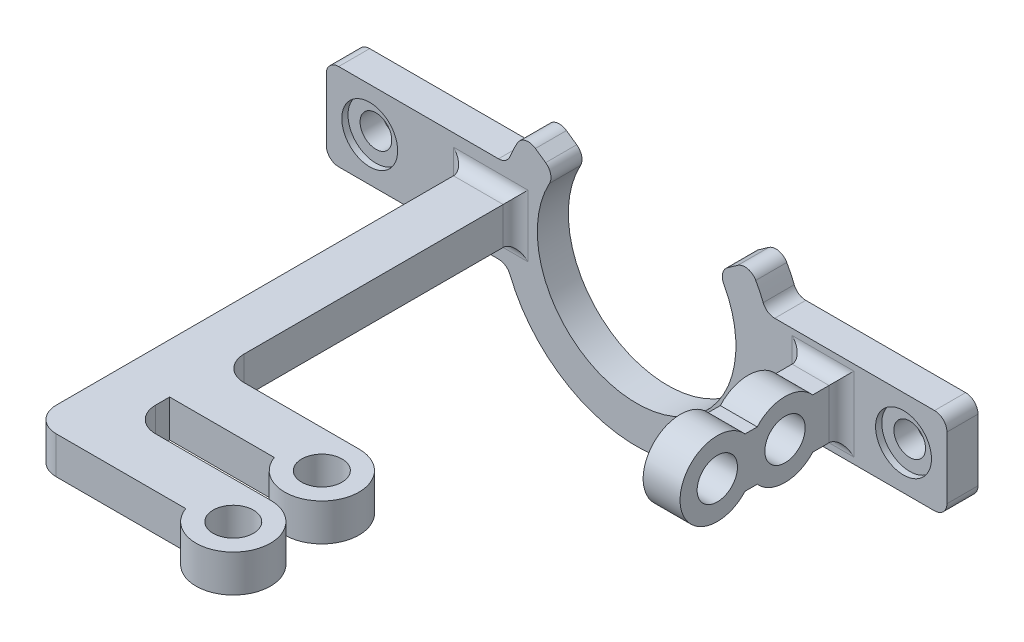
SolidWorks part; units mm, degrees
note: '?' marks a value the reader was unsure of.
ref_plane "Front Plane" through (0, 0, 0) normal (0, 0, 1) x (1, 0, 0)
ref_plane "Top Plane" through (0, 0, 0) normal (0, 1, 0) x (1, 0, 0)
ref_plane "Right Plane" through (0, 0, 0) normal (1, 0, 0) x (0, 0, -1)
sketch "Sketch1" plane through (0, 0, 0) normal (0, 0, 1) x (1, 0, 0)
  line L0 (100, 25) -> (100, 20)
  line L1 (100, 5) -> (100, 45) construction
  line L3 (98, 18) -> (72.2486, 18)
  line L4 (100, 25) -> (100, 30)
  line L5 (78.9438, 32) -> (98, 32)
  line L7 (78.9438, 32) -> (72.2486, 32)
  line L8 (54, 25) -> (106.793, 25) construction
  line L9 (50, 29) -> (50, 55.0668) construction
  line L16 (50, 25) -> (93.1322, 55.2015) construction
  line L17 (64.6534, 35.2604) -> (66.3009, 36.414)
  line L18 (50, 25) -> (6.8678, 55.2015) construction
  line L19 (46, 25) -> (-6.793, 25) construction
  line L20 (35.3466, 35.2604) -> (33.6991, 36.414)
  line L21 (21.0562, 32) -> (27.7514, 32)
  line L22 (2, 18) -> (27.7514, 18)
  line L23 (21.0562, 32) -> (2, 32)
  line L24 (0, 25) -> (0, 30)
  line L25 (0, 25) -> (0, 20)
  arc A0 (70.3945, 33.25) -> (69.1929, 35.7533) centre (50, 25) ccw
  arc A1 (35.955, 32.6641) -> (64.045, 32.6641) centre (50, 25) ccw
  arc A2 (29.6055, 16.75) -> (70.3945, 16.75) centre (50, 25) ccw
  circle A3 centre (93, 25) radius 2.55
  arc A14 (98, 32) -> (100, 30) centre (98, 30) cw
  arc A15 (98, 18) -> (100, 20) centre (98, 20) ccw
  arc A16 (72.2486, 18) -> (70.3945, 16.75) centre (72.2486, 16) ccw
  arc A17 (70.3945, 33.25) -> (72.2486, 32) centre (72.2486, 34) ccw
  arc A18 (64.6534, 35.2604) -> (64.045, 32.6641) centre (65.8006, 33.6221) ccw
  arc A19 (66.3009, 36.414) -> (69.1929, 35.7533) centre (67.4481, 34.7757) cw
  arc A21 (33.6991, 36.414) -> (30.8071, 35.7533) centre (32.5519, 34.7757) ccw
  arc A22 (35.3466, 35.2604) -> (35.955, 32.6641) centre (34.1994, 33.6221) cw
  arc A23 (29.6055, 33.25) -> (27.7514, 32) centre (27.7514, 34) cw
  arc A24 (27.7514, 18) -> (29.6055, 16.75) centre (27.7514, 16) cw
  arc A25 (2, 18) -> (0, 20) centre (2, 20) cw
  arc A26 (2, 32) -> (0, 30) centre (2, 30) ccw
  circle A27 centre (7, 25) radius 2.55
  arc A29 (29.6055, 33.25) -> (30.8071, 35.7533) centre (50, 25) cw
  point P30 (50, 3)
  point P31 (63.1064, 34.1772)
  point P35 (68.0213, 37.6187)
  point P39 (100, 32)
  point P73 (0, 32)
  point P74 (31.9787, 37.6187)
  point P75 (36.8936, 34.1772)
  dimension "D2" = 22
  dimension "D4" = 16
  dimension "D9" = 2
  dimension "D8" = 2
  dimension "D11" = 5.1
  dimension "D1" = 14
  dimension "D3" = 7
  dimension "D10" = 35
extrude "Boss-Extrude1" add sketch "Sketch1" along normal blind 5
fillet "Fillet2" [suppressed] radius 1
sketch "Sketch4" plane through (0, 0, 5) normal (0, 0, 1) x (1, 0, 0)
  circle A0 centre (93, 25) radius 4.5
  circle A1 centre (7, 25) radius 4.5
  dimension "D1" = 9
  dimension "D2" = 9
extrude "Cut-Extrude2" cut sketch "Sketch4" against normal blind 1
ref_axis "Axis1" through (93, 25, 4) along (0, 0, -1)?
ref_axis "Axis2" through (50, 25, 5) along (0, 0, -1)?
ref_plane "Plane1" through (0, 25, 0) normal (0, -1, 0) x (-1, 0, 0)
sketch "Sketch6" plane through (0, 25, 0) normal (0, -1, 0) x (-1, 0, 0)
  line L0 (-72.2486, -5) -> (-98, -5) construction
  line L1 (-77.0523, -5) -> (-83, -5)
  line L4 (-83, -5) -> (-83, -25)
  line L5 (-77.0523, -5) -> (-77.0523, -25)
  line L6 (-83, -25) -> (-77.0523, -25)
  line L7 (-93, -4) -> (-93, 0) construction
  dimension "D1" = 10
  dimension "D2" = 0
extrude "Boss-Extrude2" add sketch "Sketch6" along normal blind 4 and the other way blind 4
ref_plane "Plane2" through (77.0523, 21, 5) normal (1, 0, 0) x (0, 0, -1)
sketch "Sketch11" plane through (0, 0, 0) normal (0, 0, -1) x (-1, 0, 0)
  circle A0 centre (-93, 25) radius 4.5
  circle A1 centre (-7, 25) radius 4.5
  dimension "D1" = 9
  dimension "D2" = 9
extrude "Cut-Extrude3" cut sketch "Sketch11" against normal blind 0.5
thread "Thread1" [suppressed] pitch 0.8 start angle 0, offset 0, length 0, pitch 0.8, diameter 5.1
ref_plane "Plane3" through (90.45, 25, 4) normal (0, -1, 0) x (-1, 0, 0)
sketch "Thread Profile1" plane through (90.45, 25, 4) normal (0, -1, 0) x (-1, 0, 0)
  line L0 (0, 0) -> (0, 0.8) construction
  line L11 (0, 0) -> (0, 0.7)
  line L12 (0, 0.7) -> (-0.433, 0.45)
  line L13 (-0.433, 0.45) -> (-0.433, 0.25)
  line L15 (-0.433, 0.25) -> (0, 0)
  line L17 (-0.433, 0.35) -> (0, 0.35) construction
  point P2 (0, 0)
  dimension "Pitch" = 0.8
  dimension "Profile_Angle" = 60
  dimension "Profile_Land" = 0.2
  dimension "Profile_Height" = 0.433
sketch "Sketch16" plane through (0, 25, 0) normal (0, -1, 0) x (-1, 0, 0)
  line L0 (-27.7514, -5) -> (-2, -5) construction
  line L1 (-30.4943, -5) -> (-22.4943, -5)
  line L2 (-30.4943, -5) -> (-30.4943, -48.7321)
  line L3 (-30.4943, -75) -> (-26.4943, -75)
  line L4 (-22.4943, -5) -> (-22.4943, -71)
  line L5 (-30.4943, -60.7321) -> (-47.3614, -60.7321)
  line L6 (-30.4943, -75) -> (-47.3614, -75)
  line L8 (-34.4943, -67) -> (-53.0183, -67)
  line L10 (-53.0183, -52.7321) -> (-34.4943, -52.7321)
  line L11 (-30.4943, -60.7321) -> (-30.4943, -63)
  arc A0 (-53.0183, -67) -> (-47.3614, -75) centre (-53.0183, -73) ccw
  circle A1 centre (-53.0183, -73) radius 3.25
  arc A2 (-30.4943, -63) -> (-34.4943, -67) centre (-34.4943, -63) cw
  arc A3 (-26.4943, -75) -> (-22.4943, -71) centre (-26.4943, -71) ccw
  arc A4 (-53.0183, -52.7321) -> (-47.3614, -60.7321) centre (-53.0183, -58.7321) ccw
  circle A5 centre (-53.0183, -58.7321) radius 3.25
  arc A6 (-34.4943, -52.7321) -> (-30.4943, -48.7321) centre (-34.4943, -48.7321) ccw
  dimension "D5" = 6.5
  dimension "D6" = 4
  dimension "D7" = 4
  dimension "D8" = 12
  dimension "D10" = 6.5
  dimension "D11" = 4
  dimension "D1" = 0
  dimension "D2" = 70
  dimension "D3" = 8
  dimension "D4" = 6
  dimension "D9" = 8
extrude "Boss-Extrude3" add sketch "Sketch16" along normal blind 3 and the other way blind 3
fillet "Fillet3" radius 2 8 edges at (83, 25, 5) (80.0262, 29, 5) (77.0523, 25, 5) (80.0262, 21, 5) (26.4943, 22, 5) (30.4943, 25, 5) (22.4943, 25, 5) (26.4943, 28, 5)
sketch "Sketch17" plane through (83, 0, 0) normal (1, 0, 0) x (0, 0, -1)
  line L0 (-25, 29) -> (-25, 21) construction
  arc A0 (-19.5472, 27.5034) -> (-19.5472, 22.4966) centre (-25, 25) ccw
  arc A2 (-19.5472, 22.4966) -> (-19.5472, 27.5034) centre (-14.0944, 25) ccw
  dimension "D1" = 12
  dimension "D2" = 12
extrude "Boss-Extrude4" add sketch "Sketch17" against normal up to surface (5.9477 mm away) up to face at (77.0523, 25, 16)
sketch "Sketch18" plane through (83, 0, 0) normal (1, 0, 0) x (0, 0, -1)
  circle A0 centre (-25, 25) radius 3.25
  circle A1 centre (-14.0944, 25) radius 3.25
  dimension "D1" = 6.5
  dimension "D2" = 6.5
extrude "Cut-Extrude5" cut sketch "Sketch18" against normal up to next
thread "Thread2" [suppressed] pitch 0.8 start angle 0, offset 0, length 0, pitch 0.8, diameter 5.1
ref_plane "Plane4" through (4.45, 25, 4) normal (0, -1, 0) x (-1, 0, 0)
sketch "Thread Profile2" plane through (4.45, 25, 4) normal (0, -1, 0) x (-1, 0, 0)
  line L0 (0, 0) -> (0, 0.8) construction
  line L11 (0, 0) -> (0, 0.7)
  line L12 (0, 0.7) -> (-0.433, 0.45)
  line L13 (-0.433, 0.45) -> (-0.433, 0.25)
  line L15 (-0.433, 0.25) -> (0, 0)
  line L17 (-0.433, 0.35) -> (0, 0.35) construction
  point P2 (0, 0)
  dimension "Pitch" = 0.8
  dimension "Profile_Angle" = 60
  dimension "Profile_Land" = 0.2
  dimension "Profile_Height" = 0.433
equation "\"D3@Sketch1\"=\"D1@Sketch1\"/2"
